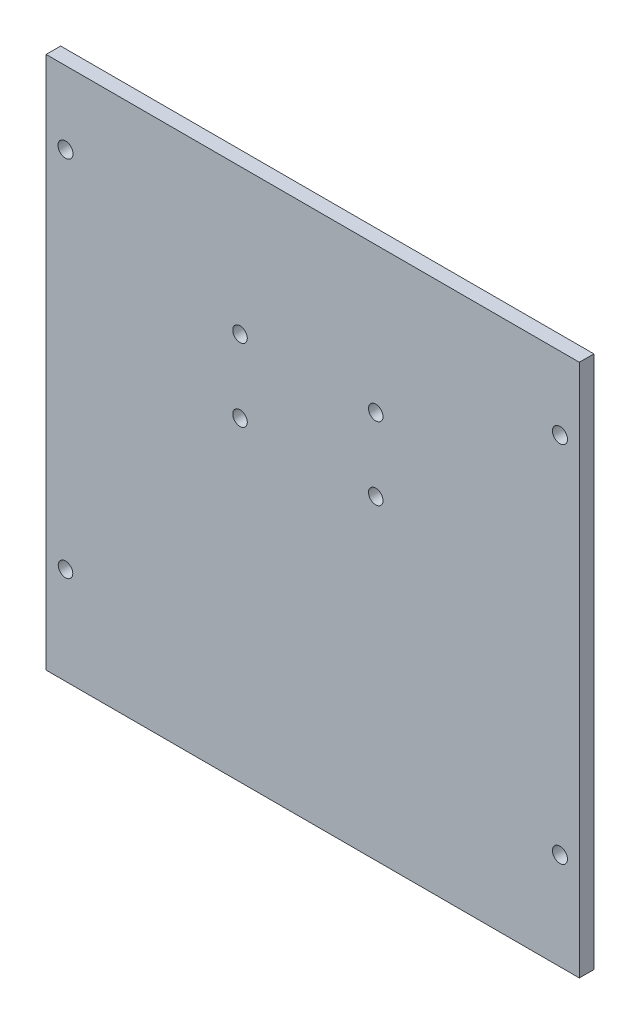
SolidWorks part; units mm, degrees
ref_plane "前视基准面" through (0, 0, 0) normal (0, 0, 1) x (1, 0, 0)
ref_plane "上视基准面" through (0, 0, 0) normal (0, 1, 0) x (1, 0, 0)
ref_plane "右视基准面" through (0, 0, 0) normal (1, 0, 0) x (0, 0, -1)
other "Configuration Table"
sketch "草图1" plane through (0, 0, 0) normal (0, 0, 1) x (1, 0, 0)
  line L1 (55, -55) -> (-55, -55)
  line L2 (55, -55) -> (55, 55)
  line L3 (55, 55) -> (-55, 55)
  line L4 (-55, -55) -> (-55, 55)
  line L5 (55, -55) -> (-55, 55) construction
  line L6 (55, 55) -> (-55, -55) construction
  point P0 (0, 0)
  dimension "D1" = 110
  dimension "D2" = 110
extrude "凸台-拉伸1" add sketch "草图1" along normal blind 3
sketch "草图2" plane through (0, 0, 0) normal (0, 0, -1) x (-1, 0, 0)
  circle A0 centre (-13, 10.02) radius 1.5
  circle A1 centre (-13, 25.02) radius 1.5
  circle A2 centre (15, 10.02) radius 1.5
  circle A3 centre (15, 25.02) radius 1.5
extrude "切除-拉伸1" cut sketch "草图2" against normal blind 10
sketch "草图3" plane through (0, 0, 0) normal (0, 0, -1) x (-1, 0, 0)
  circle A0 centre (-51, -35) radius 1.55
  circle A1 centre (-51, 40) radius 1.55
  circle A2 centre (51, -35) radius 1.5
  circle A3 centre (51, 40) radius 1.55
extrude "切除-拉伸2" cut sketch "草图3" against normal blind 10
